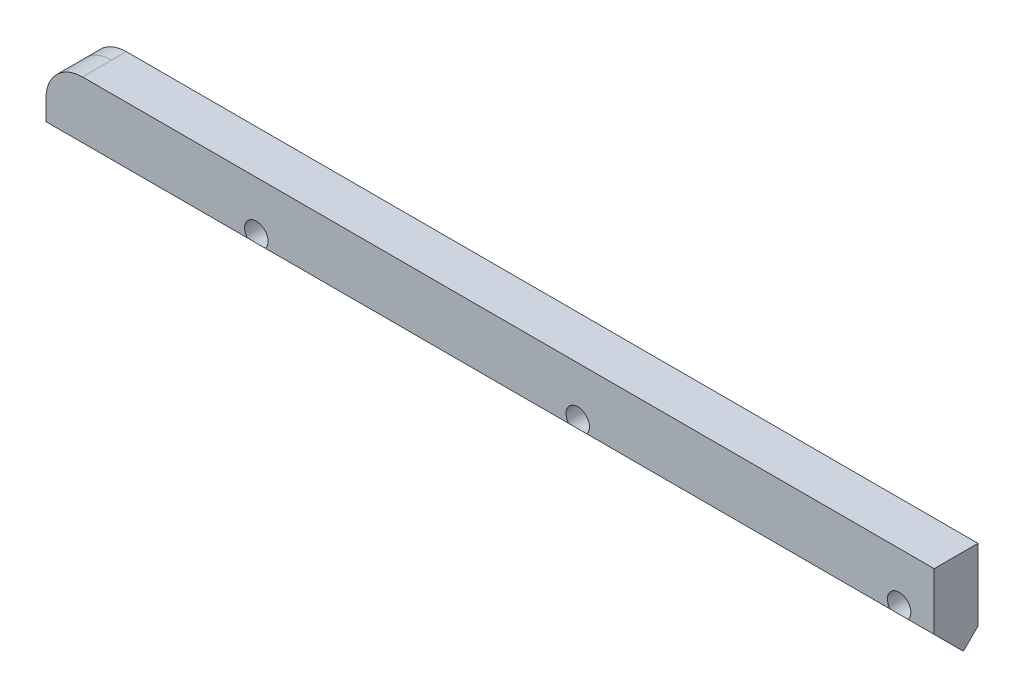
SolidWorks part; units mm, degrees
material "6061-T6 (SS)"
ref_plane "Front Plane" through (0, 0, 0) normal (0, 0, 1) x (1, 0, 0)
ref_plane "Top Plane" through (0, 0, 0) normal (0, 1, 0) x (1, 0, 0)
ref_plane "Right Plane" through (0, 0, 0) normal (1, 0, 0) x (0, 0, -1)
sketch "Sketch1" plane through (0, 0, 0) normal (1, 0, 0) x (0, 0, -1)
  line L0 (-3.0983, 0) -> (1.226, 0) construction
  line L1 (0, -3.2) -> (-2, -1.2)
  line L2 (0, -3.2) -> (0, 3.2)
  line L4 (-2, -1.2) -> (-2, 3.2)
  line L5 (-2, 3.2) -> (0, 3.2)
  dimension "D1" = 2
  dimension "D2" = 45
  dimension "D3" = 6.4
extrude "Boss-Extrude1" add sketch "Sketch1" along normal mid plane 72.8
fillet "Fillet3" radius 2.5 2 edges at (-36.4, 3.2, 1) (36.4, 3.2, 1)
sketch "Sketch5" plane through (-36.4, 0, 0) normal (-1, 0, 0) x (0, 0, 1)
  line L0 (0, -2.7) -> (2, -0.7)
  line L1 (0, -3.2) -> (0, 0.7) construction
  line L2 (2, 0.7) -> (2, -1.2) construction
  line L3 (2, -1.2) -> (0, -3.2) construction
  line L4 (2, -1.2) -> (2, -0.7)
  line L5 (2, -1.2) -> (0, -3.2)
  line L6 (0, -3.2) -> (0, -2.7)
  dimension "D1" = 0.5
extrude "Cut-Extrude5" cut sketch "Sketch5" against normal up to surface (72.8 mm away) up to face at (36.4, -0.75, 1)
sketch "Sketch7" plane through (-36.4, 0, 0) normal (-1, 0, 0) x (0, 0, 1)
  line L0 (0, -2.7) -> (-1, -1.7)
  line L1 (-1, -1.7) -> (-1, 3.2)
  line L2 (-1, 3.2) -> (0, 3.2)
  line L3 (0, 3.2) -> (0, -2.7)
  line L4 (0, 3.2) -> (2, 3.2) construction
  dimension "D1" = 45
  dimension "D2" = 3
extrude "Boss-Extrude2" add sketch "Sketch7" against normal up to surface (72.8 mm away) up to face at (36.4, -0.5, 1)
hole_wizard "M2x0.4 Tapped Hole1" positions "Sketch2" profile "Sketch3" tap size "M2x0.4" standard "ANSI Metric"
sketch "Sketch2" plane through (0, 0, 2) normal (0, 0, 1) x (1, 0, 0)
  circle A4 centre (-22, -0.2) radius 1.2 construction
  circle A5 centre (-22, -0.2) radius 1.2
  circle A8 centre (22, -0.2) radius 1.2 construction
  circle A9 centre (22, -0.2) radius 1.2
  circle A10 centre (0, -0.2) radius 1.2
  point P22 (-22, -0.2)
  point P28 (22, -0.2)
  point P31 (0, -0.2)
cosmetic thread "Hole Thread4" parameters "D1"=3, "D2"=2
cosmetic thread "Hole Thread6" parameters "D1"=3, "D2"=2
sketch "Sketch3" plane through (-22, -0.2, 2) normal (1, 0, 0) x (0, -1, 0)
  line L0 (0, 0) -> (0, 4.0807)
  line L1 (0, 4.0807) -> (0.8, 3.6)
  line L2 (0.8, 3.6) -> (0.8, 0)
  line L5 (0.8, 0) -> (0, 0)
  line L10 (0, 4.0807) -> (-0.8, 3.6) construction
  line L11 (0, -6.35) -> (0, 107.95) construction
  dimension "Tap Drill Dia." = 1.6
  dimension "Tap Drill Depth" = 3.6
  dimension "Drill Angle" = 118
cosmetic thread "Hole Thread7" parameters "D1"=3, "D2"=2
fillet "Fillet4" radius 2.5 2 edges at (-36.4, 3.2, -0.5) (36.4, 3.2, -0.5)
sketch "Sketch4" [suppressed] plane through (0, 0, 0) normal (0, 0, 1) x (1, 0, 0)
  line L1 (7.5, 1.5) -> (-7.5, 1.5)
  line L2 (7.5, 1.5) -> (7.5, -3.2)
  line L3 (7.5, -3.2) -> (-7.5, -3.2)
  line L4 (-7.5, 1.5) -> (-7.5, -3.2)
  line L5 (0, 7.7759) -> (0, -8.8374) construction
  line L8 (-7.5, -1.7) -> (-7.5, -0.7) construction
  dimension "D1" = 4.7
extrude "Cut-Extrude4" [suppressed] cut sketch "Sketch4" along normal mid plane 10
sketch "Sketch8" [suppressed] plane through (36.4, 0, 0) normal (1, 0, 0) x (0, 0, -1)
  line L1 (-1, -3.2) -> (-2, -2.2)
  line L2 (-2, -2.2) -> (-2, -1.2)
  line L3 (-2, -1.2) -> (0, -3.2)
  line L4 (0, -3.2) -> (-1, -3.2)
  dimension "D1" = 1
extrude "Boss-Extrude3" [suppressed] add sketch "Sketch8" against normal blind 3
sketch "Sketch10" [suppressed] plane through (7.5, 0, 0) normal (-1, 0, 0) x (0, 0, 1)
  line L1 (1, -3.2) -> (2, -2.2)
  line L2 (2, -2.2) -> (2, -1.2)
  line L3 (2, -1.2) -> (0, -3.2)
  line L4 (2, -2.2) -> (1, -3.2) construction
  line L5 (0, -3.2) -> (1, -3.2)
extrude "Boss-Extrude5" [suppressed] add sketch "Sketch10" against normal blind 3
mirror "Mirror1" [suppressed] about plane through (0, 0, 0) normal (1, 0, 0)
sketch "Sketch11" [suppressed] plane through (36.4, 0, 0) normal (1, 0, 0) x (0, 0, -1)
  line L0 (0, -2.7) -> (-1, -2.7)
  line L1 (-1, -2.7) -> (-2, -1.7)
  line L2 (-2, -1.7) -> (-2, -0.7)
  line L3 (0, -2.7) -> (-2, -0.7)
  dimension "D1" = 1
extrude "Boss-Extrude6" [suppressed] add sketch "Sketch11" against normal blind 3 separate body
sketch "Sketch12" [suppressed] plane through (7.5, 0, 0) normal (-1, 0, 0) x (0, 0, 1)
  line L0 (0, -2.7) -> (1, -2.7)
  line L1 (1, -2.7) -> (2, -1.7)
  line L2 (2, -1.7) -> (2, -0.7)
  line L3 (0, -2.7) -> (2, -0.7)
  line L4 (1, -2.7) -> (0, -2.7) construction
  line L5 (2, -1.7) -> (1, -2.7) construction
extrude "Boss-Extrude7" [suppressed] add sketch "Sketch12" against normal blind 3
mirror "Mirror7" [suppressed] about plane through (0, 0, 0) normal (1, 0, 0) of bodies 112 111
sketch "Sketch13" plane through (0, 0, 2) normal (0, 0, 1) x (1, 0, 0)
  line L0 (24.4, 3.2) -> (24.4, -2.7)
  line L1 (33.9, 3.2) -> (-33.9, 3.2) construction
  line L2 (36.4, -2.7) -> (-36.4, -2.7) construction
  line L4 (24.4, -2.7) -> (36.4, -2.7)
  line L5 (36.4, -2.7) -> (36.4, 3.2)
  line L6 (36.4, 3.2) -> (24.4, 3.2)
  dimension "D1" = 12
extrude "Cut-Extrude6" cut sketch "Sketch13" against normal up to surface (3 mm away) up to face at (-22.8, -0.2, -1)
